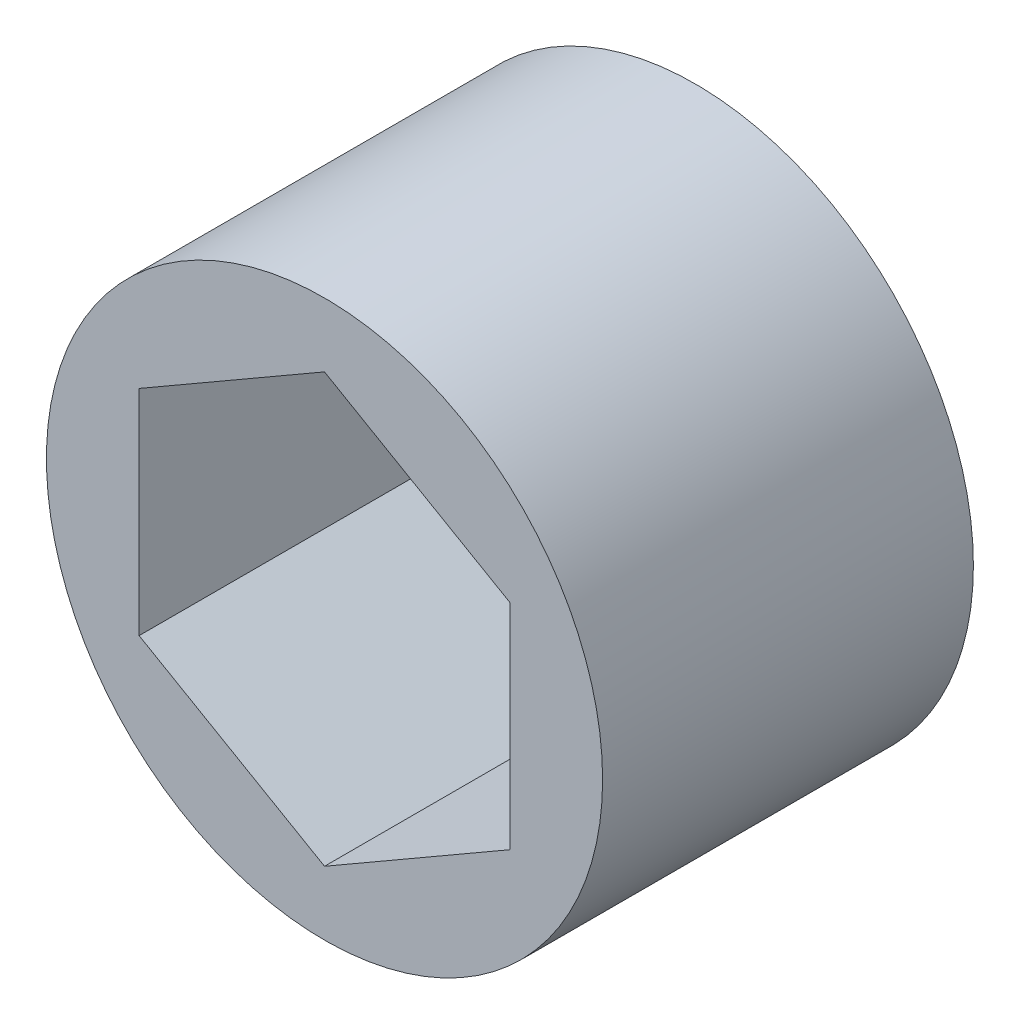
SolidWorks part; units mm, degrees
ref_plane "Front Plane" through (0, 0, 0) normal (0, 0, 1) x (1, 0, 0)
ref_plane "Top Plane" through (0, 0, 0) normal (0, 1, 0) x (1, 0, 0)
ref_plane "Right Plane" through (0, 0, 0) normal (1, 0, 0) x (0, 0, -1)
sketch "Sketch1" plane through (0, 0, 0) normal (0, 0, 1) x (1, 0, 0)
  line L1 (0, 7.3323) -> (-6.35, 3.6662)
  line L2 (-6.35, 3.6662) -> (-6.35, -3.6662)
  line L3 (-6.35, -3.6662) -> (0, -7.3323)
  line L4 (0, -7.3323) -> (6.35, -3.6662)
  line L5 (6.35, -3.6662) -> (6.35, 3.6662)
  line L6 (6.35, 3.6662) -> (0, 7.3323)
  circle A0 centre (0, 0) radius 6.35 construction
  circle A1 centre (0, 0) radius 9.525
  point P10 (0, 0)
  dimension "D1" = 12.7
  dimension "D2" = 19.05
extrude "Boss-Extrude1" add sketch "Sketch1" along normal blind 12.7
